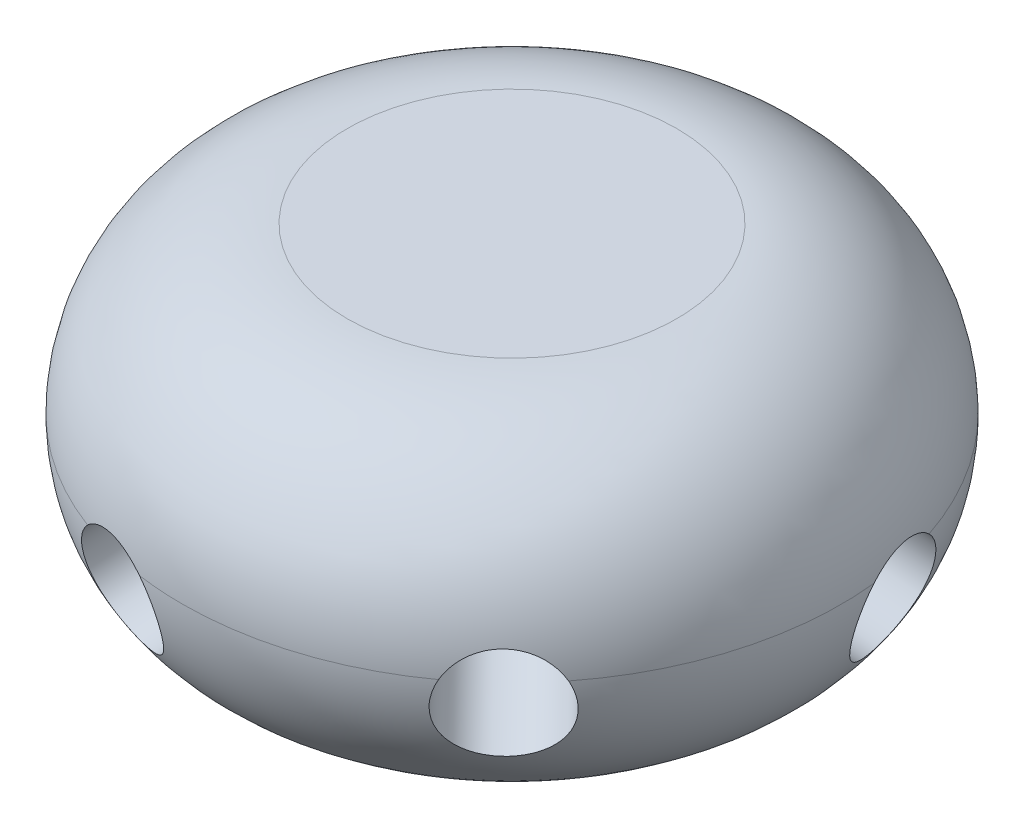
SolidWorks part; units mm, degrees
ref_plane "Front Plane" through (0, 0, 0) normal (0, 0, 1) x (1, 0, 0)
ref_plane "Top Plane" through (0, 0, 0) normal (0, 1, 0) x (1, 0, 0)
ref_plane "Right Plane" through (0, 0, 0) normal (1, 0, 0) x (0, 0, -1)
sketch "Sketch1" plane through (0, 0, 0) normal (0, 1, 0) x (1, 0, 0)
  circle A0 centre (0, 0) radius 10
  dimension "D1" = 20
extrude "base" add sketch "Sketch1" along normal blind 3 and the other way blind 7
ref_axis "6hubaxis" through (0, 5.5, 0) along (0, -1, 0)
ref_plane "Plane1" through (2.6705, -1.0931, 2.7701) normal (-0.6676, 0.2733, -0.6925) x (-0.6559, 0.2243, 0.7208)
sketch "Sketch2" plane through (2.6705, -1.0931, 2.7701) normal (-0.6676, 0.2733, -0.6925) x (-0.6559, 0.2243, 0.7208)
  circle A0 centre (0, 0) radius 1.5 construction
  circle A1 centre (0, 0) radius 1.5 construction
  circle A2 centre (0, 0) radius 1.6
  dimension "D1" = 3.2
extrude "hole1" cut sketch "Sketch2" against normal through all
pattern_circular "hole1mirror" count 2 over 360 about axis through (0, 5.5, 0) along (0, -1, 0) of "hole1"
ref_plane "Plane2" through (-0.9417, -1.2361, 3.6858) normal (0.2354, 0.309, -0.9215) x (-0.9719, 0.0738, -0.2235)
sketch "Sketch3" plane through (-0.9417, -1.2361, 3.6858) normal (0.2354, 0.309, -0.9215) x (-0.9719, 0.0738, -0.2235)
  circle A0 centre (0, 0) radius 1.5 construction
  circle A1 centre (0, 0) radius 1.5 construction
  circle A2 centre (0, 0) radius 1.6
  dimension "D1" = 3.2
extrude "hole2" cut sketch "Sketch3" against normal through all
pattern_circular "hole2mirror" count 2 over 360 about axis through (0, 5.5, 0) along (0, -1, 0) of "hole2"
ref_plane "Plane3" through (-3.7178, -1.2361, 0.8061) normal (0.9295, 0.309, -0.2015) x (-0.1912, -0.0636, -0.9795)
sketch "Sketch4" plane through (-3.7178, -1.2361, 0.8061) normal (0.9295, 0.309, -0.2015) x (-0.1912, -0.0636, -0.9795)
  circle A0 centre (0, 0) radius 1.5 construction
  circle A1 centre (0, 0) radius 1.5 construction
  circle A2 centre (0, 0) radius 1.6
  dimension "D1" = 3.2
extrude "hole3" cut sketch "Sketch4" against normal through all
pattern_circular "hole3mirror" count 2 over 360 about axis through (0, 5.5, 0) along (0, -1, 0) of "hole3"
fillet "Fillet1" radius 5 2 edges at (0, -7, 10) (0, 3, 10)
